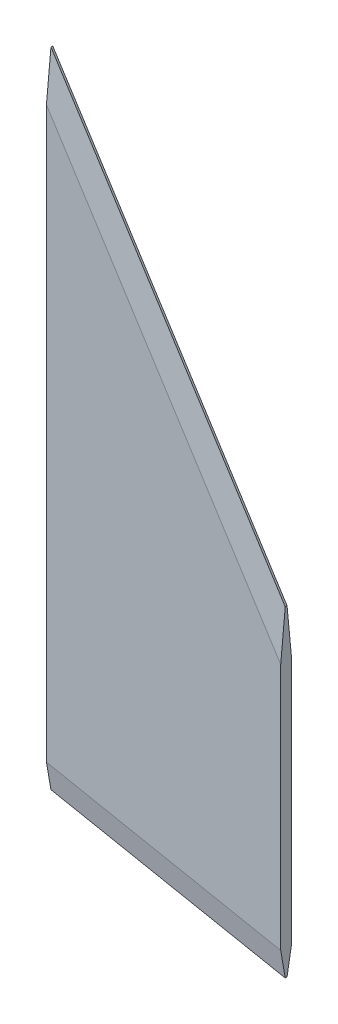
SolidWorks part; units mm, degrees
material "Hexcel AS4C (3000 Filaments)"
ref_plane "Front Plane" through (0, 0, 0) normal (0, 0, 1) x (1, 0, 0)
ref_plane "Top Plane" through (0, 0, 0) normal (0, 1, 0) x (1, 0, 0)
ref_plane "Right Plane" through (0, 0, 0) normal (1, 0, 0) x (0, 0, -1)
sketch "Sketch1" plane through (0, 0, 0) normal (0, 0, 1) x (1, 0, 0)
  line L0 (-60.9816, 89.8065) -> (-60.9816, -87.9935)
  line L1 (-60.9816, -87.9935) -> (3.7884, -100.6935)
  line L2 (3.7884, -100.6935) -> (3.7884, -11.7935)
  line L3 (3.7884, -11.7935) -> (-60.9816, 89.8065)
extrude "Boss-Extrude1" add sketch "Sketch1" along normal mid plane 3
chamfer "Chamfer1" distance 1.25 angle 80 4 edges at (-28.5966, -94.3435, -1.5) (-28.5966, -94.3435, 1.5) (-28.5966, 39.0065, -1.5) (-28.5966, 39.0065, 1.5) first distance on face at (-28.5966, -94.3435, 0) first distance on face at (-28.5966, 39.0065, 0)
